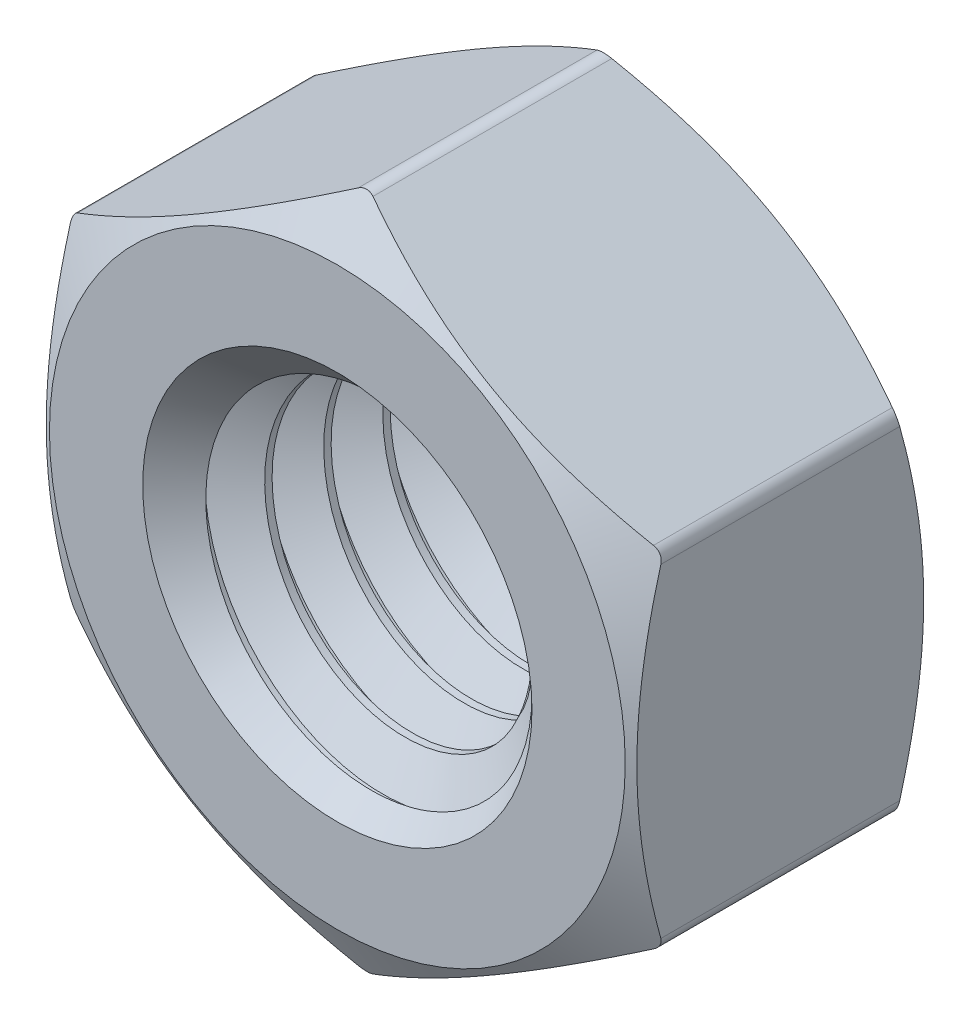
SolidWorks part; units mm, degrees
material "Alloy Steel"
ref_plane "Front Plane" through (0, 0, 0) normal (0, 0, 1) x (1, 0, 0)
ref_plane "Top Plane" through (0, 0, 0) normal (0, 1, 0) x (1, 0, 0)
ref_plane "Right Plane" through (0, 0, 0) normal (1, 0, 0) x (0, 0, -1)
sketch "Sketch1" plane through (0, 0, 0) normal (1, 0, 0) x (0, 0, -1)
  line L0 (-2, 0) -> (2, 0) construction
  line L1 (-2, -4) -> (-2, 4) construction
  line L2 (2, -4) -> (2, 4) construction
  line L3 (-2, -2.5) -> (-2, 2.5) construction
  line L4 (-2.75, 2.5866) -> (-2.35, 1.8938) construction
  line L5 (-2.35, 1.8938) -> (-1.95, 2.5866) construction
  line L6 (-1.95, 2.5866) -> (-2.75, 2.5866) construction
  line L7 (-2.725, 2.5433) -> (-1.975, 2.5433) construction
  line L8 (-2.7, 2.5) -> (-2, 2.5) construction
  line L9 (-2.4, 1.9804) -> (-2.3, 1.9804) construction
  line L10 (-2.35, 1.9804) -> (-2.35, 1.8938) construction
  line L11 (-2.35, 2.5866) -> (-2.35, 2.5) construction
  line L12 (-2, 2.6366) -> (-1.8634, 2.5) construction
  point P4 (0, 0)
  point P7 (-2, 0)
  point P11 (2, 0)
  point P14 (-2, 0)
  point P26 (-2.35, 2.5433)
  point P27 (-2, -2.5)
  dimension "Height" = 4
  dimension "Width" = 8
  dimension "Thread Size" = 5
  dimension "D1" = 60
  dimension "Thread Pitch" = 0.8
  dimension "D2" = 0.1
  dimension "D3" = 45
sketch "Sketch2" plane through (0, 0, 0) normal (0, 0, 1) x (1, 0, 0)
  line L1 (0, 4.6188) -> (-4, 2.3094)
  line L2 (-4, 2.3094) -> (-4, -2.3094)
  line L3 (-4, -2.3094) -> (0, -4.6188)
  line L4 (0, -4.6188) -> (4, -2.3094)
  line L5 (4, -2.3094) -> (4, 2.3094)
  line L6 (4, 2.3094) -> (0, 4.6188)
  circle A0 centre (0, 0) radius 4 construction
  circle A1 centre (0, 0) radius 2.5
extrude "Boss-Extrude1" add sketch "Sketch2" along normal up to vertex (2 mm away) and the other way up to vertex (2 mm away) up to point (0, -4, 2) other way up to point (0, -4, -2)
sketch "Sketch3" plane through (0, 0, 2) normal (0, 0, 1) x (1, 0, 0)
  circle A0 centre (0, 0) radius 3.9
  dimension "D1" = 7.8
extrude "Cut-Extrude1" cut sketch "Sketch3" against normal through all draft 60 flip side to cut
fillet "Fillet1" radius 0.2 6 edges at (4, -2.3094, -0.2075) (0, -4.6188, -0.2075) (-4, -2.3094, -0.2075) (-4, 2.3094, -0.2075) (4, 2.3094, -0.2075) (0, 4.6188, -0.2075)
sketch "Sketch8" plane through (0, 0, 2) normal (0, 0, 1) x (1, 0, 0)
  circle A0 centre (0, 0) radius 2.6366
extrude "Cut-Extrude4" cut sketch "Sketch8" against normal through all draft 45
mirror "Mirror1" about plane through (0, 0, 0) normal (0, 0, 1) of "Cut-Extrude4", "Cut-Extrude1"
sketch "Sketch4" plane through (0, 0, 0) normal (1, 0, 0) x (0, 0, -1)
  line L1 (-2.725, 2.5433) -> (-2.4, 1.9804)
  line L2 (-2.4, 1.9804) -> (-2.3, 1.9804)
  line L3 (-2.3, 1.9804) -> (-1.975, 2.5433)
  line L4 (-2.725, 2.5433) -> (-1.975, 2.5433) construction
  line L5 (-2.725, 2.5433) -> (-1.975, 2.5433)
sketch "Sketch5" plane through (0, 0, 2) normal (0, 0, 1) x (1, 0, 0)
  circle A0 centre (0, 0) radius 2.5 construction
  circle A1 centre (0, 0) radius 2.5
curve "Helix/Spiral1" pitch 0.8 height 4.8 radius 2.5 centre (0, 0, 2) axis (0, 0, -1) start towards (0, 1, 0)
sweep "Sweep1" add profiles "Sketch4" path "Helix/Spiral1"
sketch "Sketch6" plane through (0, 0, 2) normal (0, 0, 1) x (1, 0, 0)
  circle A0 centre (0, 0) radius 2.6366 construction
  circle A1 centre (0, 0) radius 2.6366
extrude "Cut-Extrude2" cut sketch "Sketch6" along normal through all and the other way through all draft 45
sketch "Sketch7" plane through (0, 0, -2) normal (0, 0, -1) x (-1, 0, 0)
  circle A1 centre (0, 0) radius 2.6366
  circle A2 centre (0, 0) radius 2.6366
  dimension "D1" = 0
extrude "Cut-Extrude3" cut sketch "Sketch7" along normal through all and the other way through all draft 45
equation "\"D2@Sketch1\"=\"Thread Pitch@Sketch1\"/8"
equation "\"D4@Helix/Spiral1\"=\"Thread Pitch@Sketch1\""
equation "\"D3@Helix/Spiral1\"=\"Height@Sketch1\"+\"Thread Pitch@Sketch1\""
equation "\"D1@Sketch3\"=\"Width@Sketch1\"*.975"
equation "\"D1@Fillet1\"=\"Width@Sketch1\"*.025"
